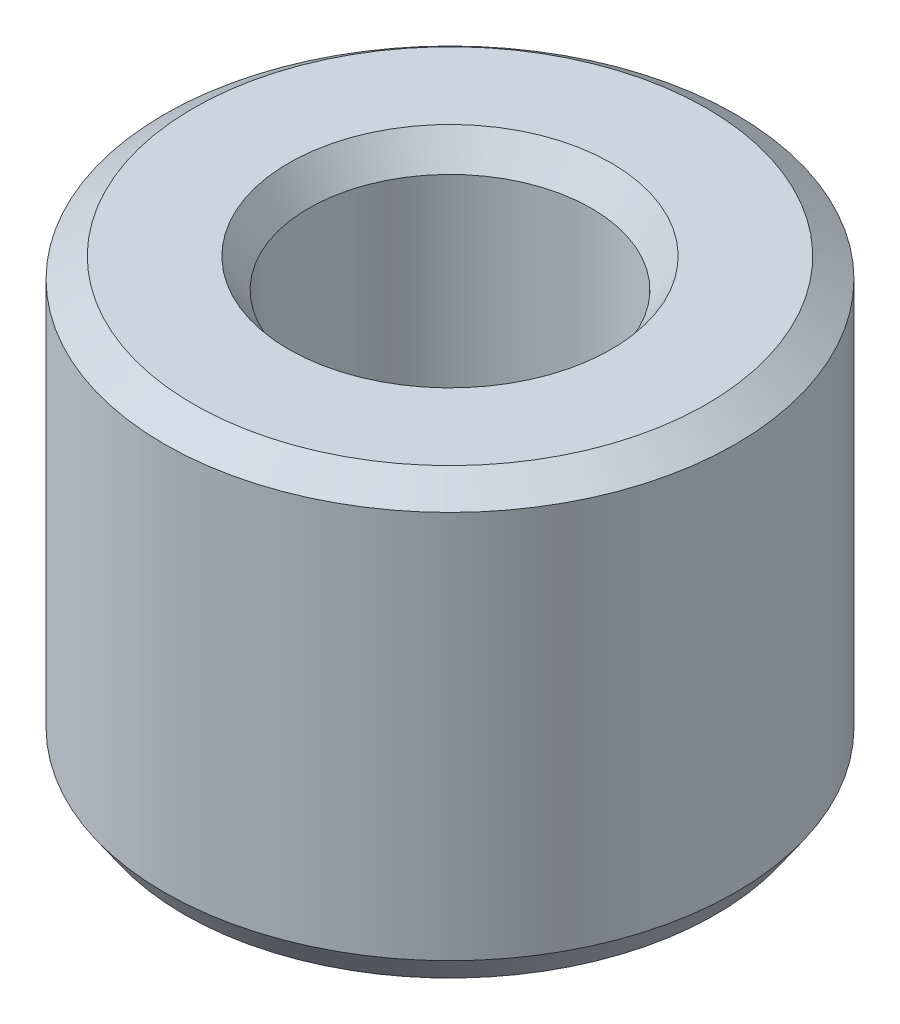
SolidWorks part; units mm, degrees
ref_plane "Front Plane" through (0, 0, 0) normal (0, 0, 1) x (1, 0, 0)
ref_plane "Top Plane" through (0, 0, 0) normal (0, 1, 0) x (1, 0, 0)
ref_plane "Right Plane" through (0, 0, 0) normal (1, 0, 0) x (0, 0, -1)
sketch "Sketch1" plane through (0, 0, 0) normal (0, 1, 0) x (1, 0, 0)
  circle A0 centre (0, 0) radius 50
  dimension "SLEEVE_OD" = 100
extrude "Boss-Extrude1" add sketch "Sketch1" along normal blind 76.5487
sketch "Sketch2" plane through (0, 0, 0) normal (0, 1, 0) x (1, 0, 0)
  circle A0 centre (0, 0) radius 24.7464
  dimension "BORE_D" = 49.4928
extrude "Cut-Extrude1" cut sketch "Sketch2" along normal through all
chamfer "Chamfer1" distance 3.4943 angle 55.585 4 edges at (0, 76.5487, 24.7464) (0, 0, 24.7464) (0, 0, 50) (0, 76.5487, 50) first distance on face at (0, 76.5487, 24.7464) first distance on face at (0, 0, 24.7464) first distance on face at (0, 76.5487, 50)
